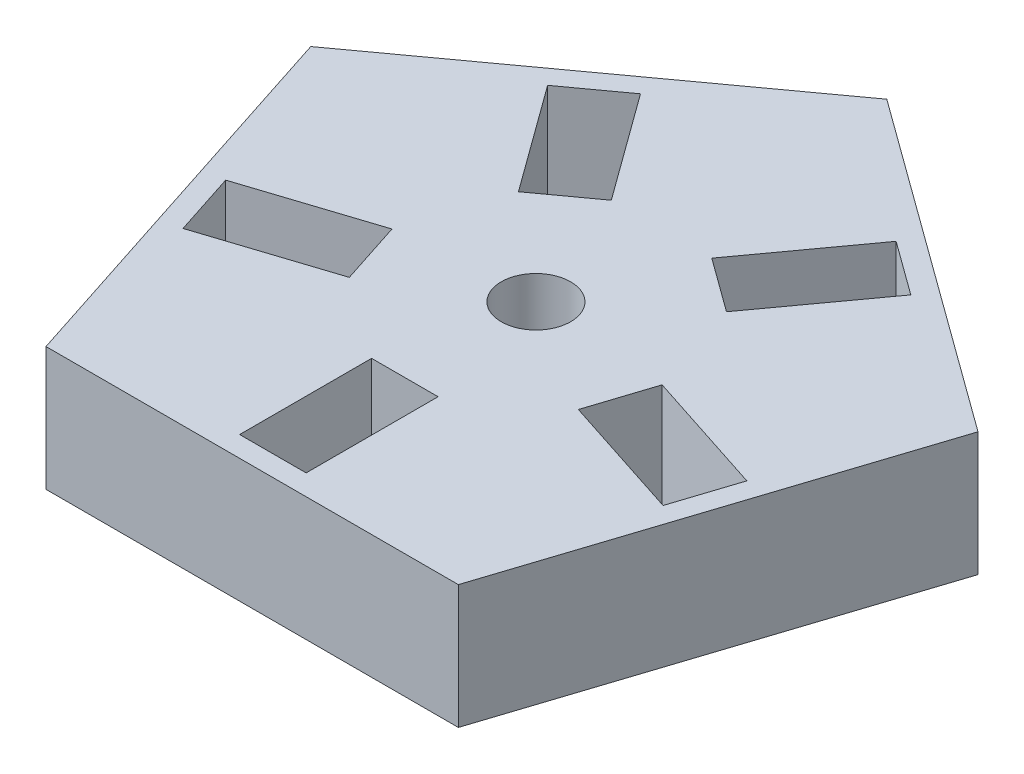
SolidWorks part; units mm, degrees
ref_plane "Front Plane" through (0, 0, 0) normal (0, 0, 1) x (1, 0, 0)
ref_plane "Top Plane" through (0, 0, 0) normal (0, 1, 0) x (1, 0, 0)
ref_plane "Right Plane" through (0, 0, 0) normal (1, 0, 0) x (0, 0, -1)
sketch "Sketch4" plane through (0, 0, 0) normal (0, 1, 0) x (1, 0, 0)
  line L0 (-102.7473, 33.4025) -> (0, 108.0483)
  line L1 (0, 108.0483) -> (102.743, 33.3966)
  line L2 (102.743, 33.3966) -> (63.4943, -87.3864)
  line L3 (63.4943, -87.3864) -> (-63.5057, -87.3828)
  line L4 (-63.5057, -87.3828) -> (-102.7473, 33.4025)
  circle A0 centre (0, 0) radius 6.1263
  dimension "D1" = 108
  dimension "D2" = 108
  dimension "D3" = 108
  dimension "D4" = 108
  dimension "D5" = 108.0483
  dimension "D6" = 127
  dimension "D7" = 127
  dimension "D8" = 127
extrude "Boss-Extrude2" add sketch "Sketch4" along normal blind 38.1 contours L0 L1 L2 L3 L4
ref_axis "Axis3" through (0, -1.905, 0) along (0, 1, 0)
sketch "Sketch5" plane through (0, 38.1, 0) normal (0, 1, 0) x (1, 0, 0)
  line L0 (63.4943, -87.3864) -> (-63.5057, -87.3828) construction
  line L1 (10.2559, -81.0346) -> (-10.2165, -81.0346)
  line L2 (10.2559, -81.0346) -> (10.2559, -40.3946)
  line L3 (10.2559, -40.3946) -> (-10.2165, -40.3946)
  line L4 (-10.2165, -81.0346) -> (-10.2165, -40.3946)
  point P6 (0.0197, -81.0346)
  dimension "D1" = 20.4724
  dimension "D2" = 40.64
  dimension "D3" = 6.35
  dimension "D4" = 53.2384
extrude "Cut-Extrude2" cut sketch "Sketch5" against normal through all
pattern_circular "CirPattern1" count 5 every 72 about axis through (0, -1.905, 0) along (0, 1, 0) of "Cut-Extrude2"
sketch "Sketch6" plane through (0, 0, 0) normal (0, -1, 0) x (1, 0, 0)
  circle A0 centre (0, 0) radius 10.6807
extrude "Cut-Extrude3" cut sketch "Sketch6" against normal through all
